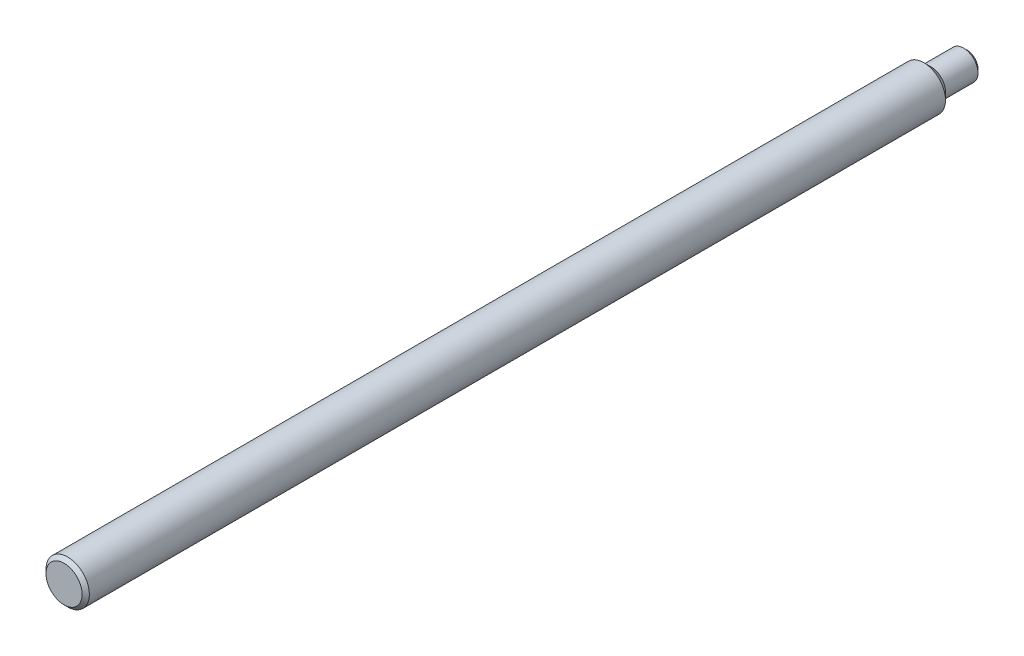
SolidWorks part; units mm, degrees
ref_plane "Piano frontale" through (0, 0, 0) normal (0, 0, 1) x (1, 0, 0)
ref_plane "Piano superiore" through (0, 0, 0) normal (0, 1, 0) x (1, 0, 0)
ref_plane "Piano destro" through (0, 0, 0) normal (1, 0, 0) x (0, 0, -1)
sketch "Schizzo1" plane through (0, 0, 0) normal (0, 0, 1) x (1, 0, 0)
  circle A0 centre (0, 0) radius 6
  dimension "D1" = 12
extrude "Estrusione-Estrusione1" add sketch "Schizzo1" along normal blind 250
cosmetic thread "Filettatura cosmetica1" parameters "D2"=10.344
sketch "Schizzo2" plane through (0, 0, 0) normal (0, 1, 0) x (1, 0, 0)
  line L0 (0, 1.8987) -> (0, -61.2971) construction
  line L1 (-4, -10) -> (-6, -12)
  line L2 (-6, -12) -> (-6, 0)
  line L3 (-6, 0) -> (-4, 0)
  line L4 (-4, 0) -> (-4, -10)
  line L5 (-6, 0) -> (-6, -250) construction
  line L6 (6, 0) -> (-6, 0) construction
  dimension "D1" = 8
  dimension "D2" = 135
  dimension "D3" = 10
revolve "Taglia-Rivoluzione1" cut sketch "Schizzo2" angle 360 about L0
chamfer "Smusso1" distance 1 angle 45 2 edges at (-4, 0, 0) (6, 0, 250)
sketch "Schizzo3" plane through (0, 0, 0) normal (0, 1, 0) x (1, 0, 0)
  line L0 (-4, -10) -> (-4, -10.2926)
